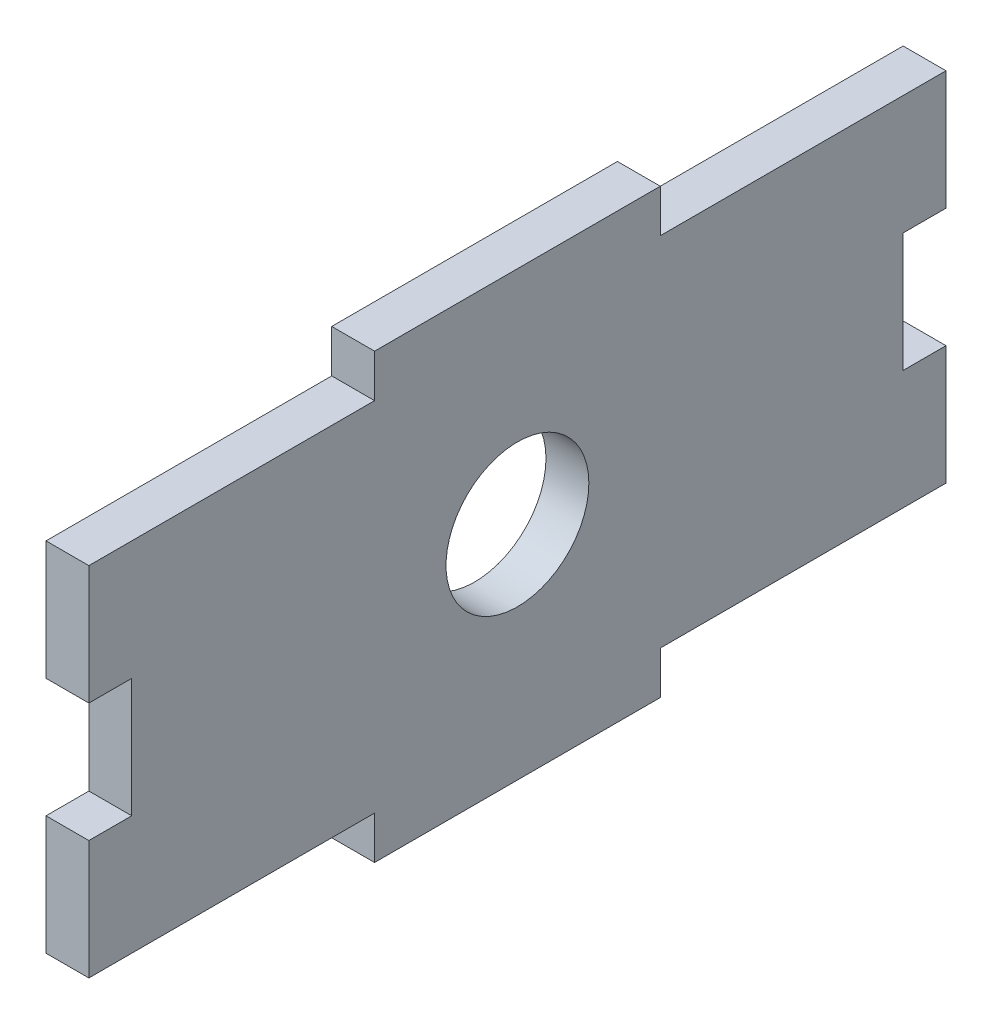
SolidWorks part; units mm, degrees
ref_plane "Front Plane" through (0, 0, 0) normal (0, 0, 1) x (1, 0, 0)
ref_plane "Top Plane" through (0, 0, 0) normal (0, 1, 0) x (1, 0, 0)
ref_plane "Right Plane" through (0, 0, 0) normal (1, 0, 0) x (0, 0, -1)
sketch "Sides" plane through (0, 0, 0) normal (1, 0, 0) x (0, 0, -1)
  line L0 (0, 16.6667) -> (0, 25)
  line L1 (0, 0) -> (20, 0)
  line L2 (0, 0) -> (0, 8.3333)
  line L3 (0, 25) -> (20, 25)
  line L4 (60, 0) -> (60, 8.3333)
  line L5 (0, 16.6667) -> (3, 16.6667)
  line L6 (40, 25) -> (60, 25)
  line L7 (0, 8.3333) -> (3, 8.3333)
  line L8 (3, 16.6667) -> (3, 8.3333)
  line L9 (40, 0) -> (60, 0)
  line L10 (20, 25) -> (20, 28)
  line L11 (20, 28) -> (40, 28)
  line L12 (40, 25) -> (40, 28)
  line L13 (60, 16.6667) -> (60, 25)
  line L14 (40, 0) -> (40, -3)
  line L15 (20, 0) -> (20, -3)
  line L16 (20, -3) -> (40, -3)
  line L17 (60, 16.6667) -> (57, 16.6667)
  line L18 (60, 8.3333) -> (57, 8.3333)
  line L19 (57, 16.6667) -> (57, 8.3333)
  circle A0 centre (30, 12.5) radius 5
  dimension "D9" = 15.5
  dimension "D1" = 25
  dimension "D2" = 60
  dimension "D3" = 8.3333
  dimension "D4" = 8.3333
  dimension "D5" = 3
  dimension "D6" = 20
  dimension "D7" = 3
  dimension "D8" = 20
  dimension "D10" = 27
  dimension "D11" = 20
  dimension "D12" = 20
extrude "Sides Extruded" add sketch "Sides" along normal blind 3
